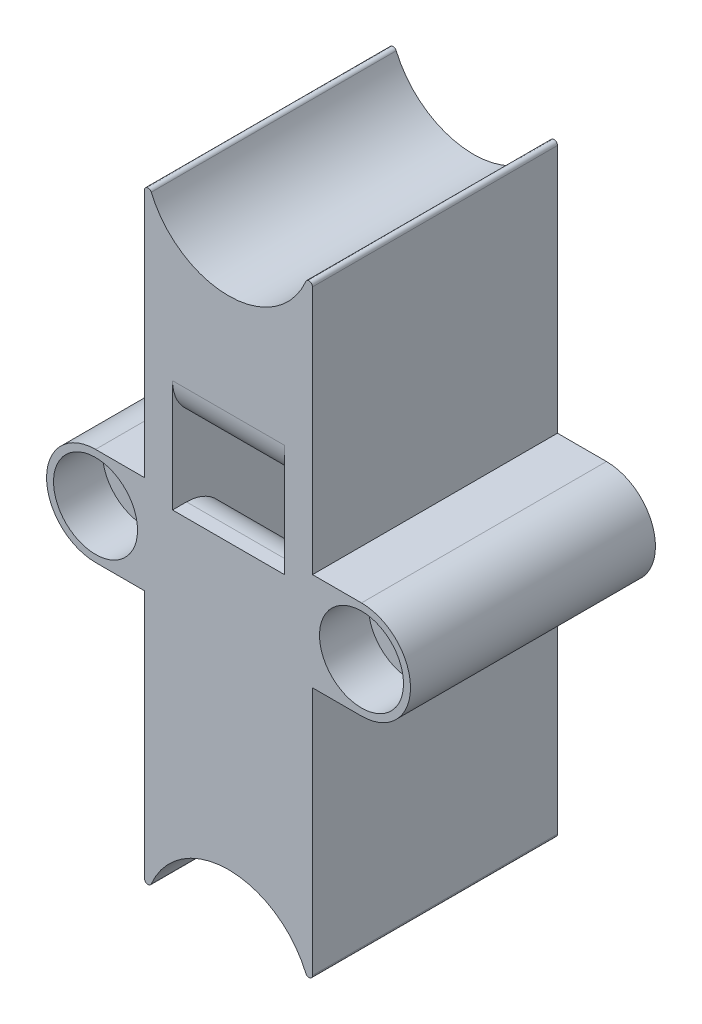
SolidWorks part; units mm, degrees
ref_plane "Front Plane" through (0, 0, 0) normal (0, 0, 1) x (1, 0, 0)
ref_plane "Top Plane" through (0, 0, 0) normal (0, 1, 0) x (1, 0, 0)
ref_plane "Right Plane" through (0, 0, 0) normal (1, 0, 0) x (0, 0, -1)
sketch "Sketch1" plane through (0, 0, 0) normal (0, 0, 1) x (1, 0, 0)
  line L0 (0, 0) -> (-14, 0) construction
  line L1 (-6, -23.75) -> (6, -23.75)
  line L2 (-6, -23.75) -> (-6, 23.75)
  line L3 (-6, 23.75) -> (6, 23.75)
  line L4 (6, -23.75) -> (6, 23.75)
  line L5 (-6, -23.75) -> (6, 23.75) construction
  line L6 (-6, 23.75) -> (6, -23.75) construction
  line L7 (-14, 0) -> (11.9672, 0) construction
  line L8 (-6, 3.5) -> (-9.5, 3.5)
  line L9 (-6, -3.5) -> (-9.5, -3.5)
  line L10 (6, 3.5) -> (9.5, 3.5)
  line L11 (6, -3.5) -> (9.5, -3.5)
  circle A0 centre (0, 23.75) radius 6
  circle A1 centre (0, -23.75) radius 6
  circle A2 centre (9.5, 0) radius 3.5
  circle A3 centre (-9.5, 0) radius 3.5
  circle A4 centre (-9.5, 0) radius 1.65
  circle A5 centre (9.5, 0) radius 1.65
  point P0 (0, 0)
  dimension "D1" = 12
  dimension "D2" = 47.5
extrude "Boss-Extrude1" add sketch "Sketch1" along normal blind 17.5 contours A1 L4 A0 L2 | A3 L2 L8 | A3 L9 L2 | A3 A4 | A2 A5 | A2 L10 L4 | A2 L4 L11 region at (0, 0, 0) region at (-6.7818, -2.7182, 0) region at (6.7818, -2.7182, 0) region at (-6.7818, 2.7182, 0) region at (-7.0951, -2.4049, 0) region at (6.7818, 2.7182, 0) region at (7.0951, 2.4049, 0)
fillet "Fillet1" radius 0.25 4 edges at (-6, -23.75, 8.75) (6, -23.75, 8.75) (6, 23.75, 8.75) (-6, 23.75, 8.75)
sketch "Skizze1" plane through (0, 0, 17.5) normal (0, 0, 1) x (1, 0, 0)
  line L0 (0, 17.75) -> (0, -17.75) construction
  line L2 (-4, -2.5) -> (4, -2.5)
  line L3 (-4, -2.5) -> (-4, 2.5)
  line L4 (-4, 2.5) -> (4, 2.5)
  line L5 (4, -2.5) -> (4, 2.5)
  line L6 (-4, -2.5) -> (4, 2.5) construction
  line L7 (-4, 2.5) -> (4, -2.5) construction
  line L8 (-4, 2.5) -> (4, 2.5)
  line L9 (-4, 2.5) -> (-4, 7.5)
  line L10 (-4, 7.5) -> (4, 7.5)
  line L11 (4, 2.5) -> (4, 7.5)
  line L12 (-4, 2.5) -> (4, 7.5) construction
  line L13 (-4, 7.5) -> (4, 2.5) construction
  arc A0 (-5.52, 21.3985) -> (5.52, 21.3985) centre (0, 23.75) ccw construction
  arc A1 (5.52, -21.3985) -> (-5.52, -21.3985) centre (0, -23.75) ccw construction
  point P8 (0, 0)
  point P15 (0, 5)
  dimension "D1" = 8
  dimension "D2" = 5
  dimension "D3" = 5
extrude "Schnitt-Linear austragen1" cut sketch "Skizze1" against normal blind 8 contours L4 L11 L10 L9 region at (0, 5, 17.5)
sketch "Skizze2" plane through (0, 2.5, 0) normal (0, 1, 0) x (1, 0, 0)
  line L0 (4, -9.5) -> (4, -17.5) construction
  line L1 (-4, -17.5) -> (4, -17.5)
  line L2 (-4, -17.5) -> (-4, -9.5)
  line L3 (-4, -9.5) -> (4, -9.5)
  line L4 (4, -17.5) -> (4, -9.5)
  line L5 (-4, -17.5) -> (4, -9.5) construction
  line L6 (-4, -9.5) -> (4, -17.5) construction
  line L8 (-4, -9.5) -> (4, -9.5) construction
  line L10 (-4, -17.5) -> (4, -17.5)
  line L11 (-4, -17.5) -> (-4, -13.5)
  line L12 (-4, -13.5) -> (4, -13.5)
  line L13 (4, -17.5) -> (4, -13.5)
  line L14 (-4, -17.5) -> (4, -13.5) construction
  line L15 (-4, -13.5) -> (4, -17.5) construction
  point P4 (0, -13.5)
  point P12 (0, -15.5)
  line M8 (4, -9.5) -> (-4, -9.5)
  line M9 (-4, -9.5) -> (-4, -17.5)
  dimension "D1" = 4
extrude "Schnitt-Linear austragen2" cut sketch "Skizze2" against normal blind 10 contours L12 L4 M9 M8 region at (0, 2.5, 11.5)
fillet "Verrundung1" radius 3 2 edges at (0, 7.5, 17.5) (0, 2.5, 13.5)
sketch "Skizze3" plane through (0, 0, 17.5) normal (0, 0, 1) x (1, 0, 0)
  circle A0 centre (-9.5, 0) radius 3
  circle A1 centre (9.5, 0) radius 3
extrude "Schnitt-Linear austragen3" cut sketch "Skizze3" against normal blind 3.5
